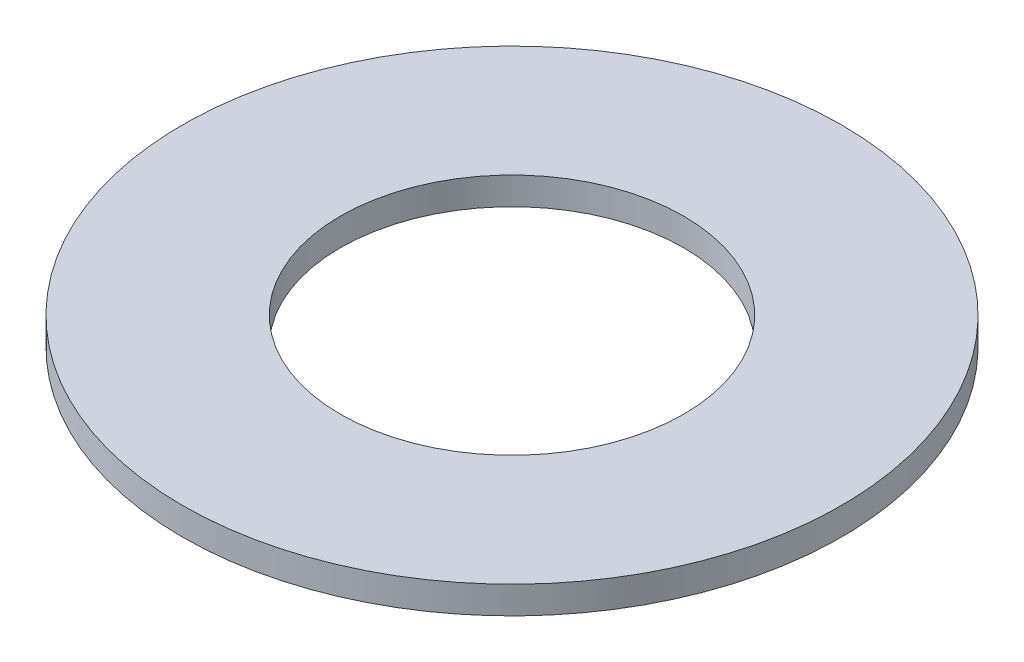
SolidWorks part; units mm, degrees
ref_plane "Front Plane" through (0, 0, 0) normal (0, 0, 1) x (1, 0, 0)
ref_plane "Top Plane" through (0, 0, 0) normal (0, 1, 0) x (1, 0, 0)
ref_plane "Right Plane" through (0, 0, 0) normal (1, 0, 0) x (0, 0, -1)
sketch "Sketch1" plane through (0, 0, 0) normal (0, 1, 0) x (1, 0, 0)
  circle A0 centre (0, 0) radius 12
  circle A1 centre (0, 0) radius 6.25
  dimension "D1" = 24
  dimension "D2" = 12.5
base flange "Base-Flange1" sketch "Sketch1" thickness 1 reverse thickness direction no parameters "D1"=5
sketch "Bend-Lines1" [suppressed] plane through (0, 0, 0) normal (0, 1, 0) x (1, 0, 0)
sketch "Bounding-Box1" [suppressed] plane through (0, 0, 0) normal (0, 1, 0) x (1, 0, 0)
sheet metal parameters "Sheet-Metal1" thickness 1 parameters "D1"=5
flat pattern "Flat-Pattern1" [suppressed]
sketch "Bend-Lines2" plane through (0, 0, 0) normal (0, 1, 0) x (1, 0, 0)
sketch3d "Bounding-Box2" [suppressed]
  line L0 (12.0014, 11.9985, 0) -> (11.9984, -12.0015, 0) construction
  line L1 (-11.9984, 12.0015, 0) -> (-12.0014, -11.9985, 0) construction
  line L2 (12.0014, 11.9985, 0) -> (-11.9984, 12.0015, 0) construction
  line L3 (11.9984, -12.0015, 0) -> (-12.0014, -11.9985, 0) construction
